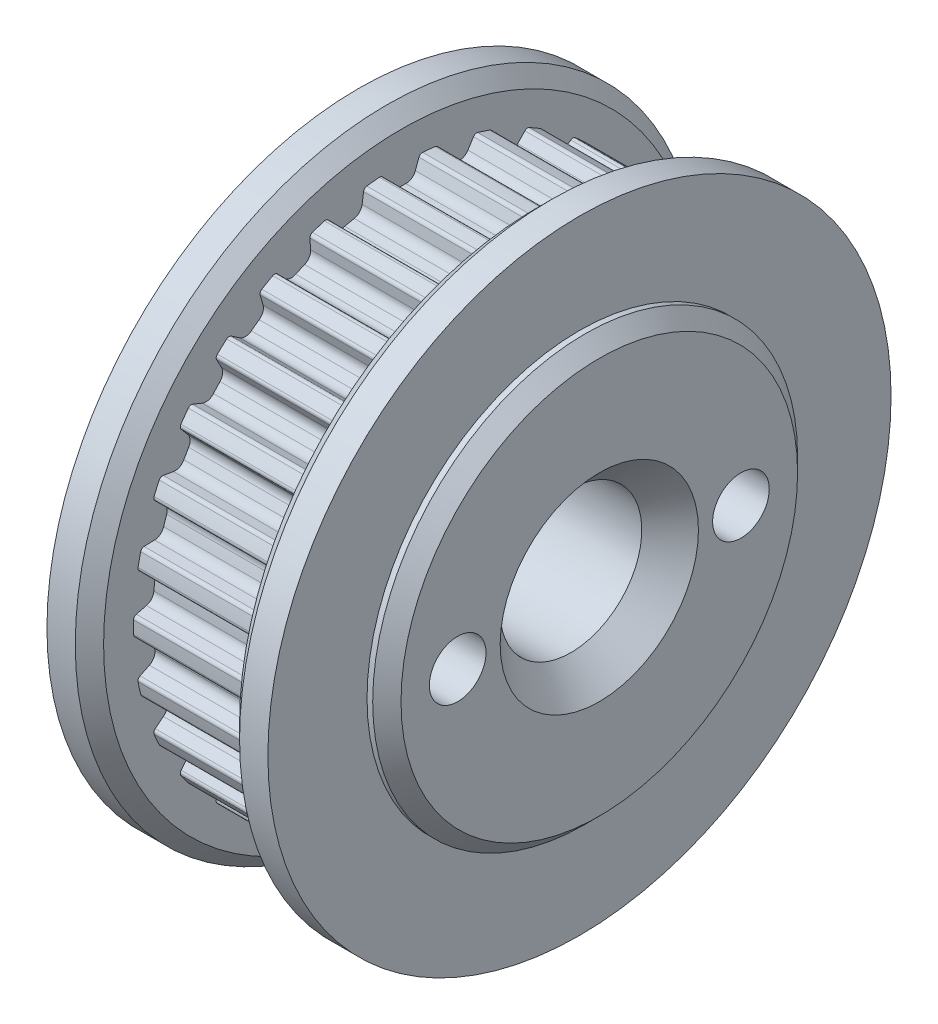
SolidWorks part; units mm, degrees
ref_plane "前视基准面" through (0, 0, 0) normal (0, 0, 1) x (1, 0, 0)
ref_plane "上视基准面" through (0, 0, 0) normal (0, 1, 0) x (1, 0, 0)
ref_plane "右视基准面" through (0, 0, 0) normal (1, 0, 0) x (0, 0, -1)
sketch "草图1" plane through (0, 0, 0) normal (0, 0, 1) x (1, 0, 0)
  line L0 (0, 0) -> (64.8368, 0) construction
  line L1 (0, 1.75) -> (0, 9.446)
  line L2 (0, 9.446) -> (4.8, 9.446)
  line L3 (4.8, 9.446) -> (4.8, 5)
  line L4 (4.8, 5) -> (7, 5)
  line L5 (7, 5) -> (7, 1.75)
  line L6 (7, 1.75) -> (0, 1.75)
  dimension "L" = 7
  dimension "B" = 4.8
  dimension "d" = 3.5
  dimension "d1" = 10
  dimension "da" = 18.892
revolve "旋转1" add sketch "草图1" angle 360 about L0
sketch "草图7" plane through (0, 0, 0) normal (-1, 0, 0) x (0, 0, 1)
  circle A1 centre (0, 0) radius 1.75 construction
  circle A2 centre (0, 0) radius 11
  circle A3 centre (0, 0) radius 1.75
  dimension "D1" = 22
extrude "凸台-拉伸1" add sketch "草图7" along normal blind 1.5
sketch "草图8" plane through (7, 0, 0) normal (1, 0, 0) x (0, 0, -1)
  circle A0 centre (0, 0) radius 2.5
  dimension "D1" = 5
extrude "切除-拉伸3" cut sketch "草图8" against normal through all
chamfer "倒角1" distance 1 angle 45 2 edges at (7, 0, -2.5) (-1.5, 0, -2.5)
ref_axis "基准轴1" through (-0.35, 0, 0) along (1, 0, 0)
sketch "草图6" plane through (0, 0, 0) normal (1, 0, 0) x (0, 0, -1)
  line L0 (0, 0) -> (0, 16.0158) construction
  line L1 (0.6325, 9.3298) -> (0.5069, 8.9846)
  line L2 (0.8947, 9.4035) -> (1.3928, 10.772)
  line L3 (-0.8947, 9.4035) -> (-1.3928, 10.772)
  line L4 (-0.6325, 9.3298) -> (-0.5069, 8.9846)
  circle A0 centre (0, 0) radius 9.446 construction
  arc A1 (0.1711, 8.7543) -> (-0.1711, 8.7543) centre (0, 0) ccw
  arc A2 (0.7652, 9.415) -> (0.8947, 9.4035) centre (0, 0) cw
  arc A3 (0.5069, 8.9846) -> (0.1711, 8.7543) centre (0.178, 9.1043) cw
  arc A4 (0.6325, 9.3298) -> (0.7652, 9.415) centre (0.7547, 9.2854) cw
  arc A5 (1.3928, 10.772) -> (-1.3928, 10.772) centre (0, 0) ccw
  arc A6 (-0.7652, 9.415) -> (-0.8947, 9.4035) centre (0, 0) ccw
  arc A7 (-0.6325, 9.3298) -> (-0.7652, 9.415) centre (-0.7547, 9.2854) ccw
  arc A8 (-0.5069, 8.9846) -> (-0.1711, 8.7543) centre (-0.178, 9.1043) ccw
  point P8 (0, 15.3258)
  point P14 (0.6662, 9.4225)
  point P16 (0.42, 8.7459)
  dimension "D1" = 8.756
  dimension "ra" = 0.13
  dimension "rf" = 0.35
  dimension "D3" = 1.4563
  dimension "D4" = 0.13
  dimension "bw" = 0.84
  dimension "angle" = 40
  dimension "hg" = 0.69
extrude "切除-拉伸2" cut sketch "草图6" along normal up to next
pattern_circular "阵列(圆周)3" count 30 over 360 about axis through (-0.35, 0, 0) along (1, 0, 0) of "切除-拉伸2"
sketch "草图10" plane through (4.8, 0, 0) normal (1, 0, 0) x (0, 0, -1)
  circle A0 centre (0, 0) radius 7.5
  circle A1 centre (0, 0) radius 5 construction
  circle A2 centre (0, 0) radius 5
  dimension "D1" = 15
extrude "凸台-拉伸3" add sketch "草图10" along normal up to surface (2.2 mm away) up to face at (7, 0, 3.5)
chamfer "倒角2" distance 0.5 angle 45 2 edges at (0, 0, 11) (7, 0, 7.5)
hole_wizard "大小mm Clearance 暗销孔1" positions "草图13" profile "草图12" hole size "Ø2.0" standard "GB" end condition through all
sketch "草图13" plane through (7, 0, 0) normal (1, 0, 0) x (0, 0, -1)
  line L0 (0, 0) -> (0, 5.1274) construction
  point P0 (-5, 0)
  point P2 (5, 0)
  dimension "D1" = 5
sketch "草图12" plane through (7, 0, 5) normal (0, 1, 0) x (0, 0, -1)
  line L0 (0, 0) -> (0, 8.5)
  line L1 (0, 8.5) -> (1, 8.5)
  line L2 (1, 8.5) -> (1, 0)
  line L5 (1, 0) -> (0, 0)
  line L11 (0, -6.35) -> (0, 107.95) construction
  dimension "通孔孔直径" = 2
  dimension "通孔孔深度" = 8.5
sketch "草图9" plane through (4.8, 0, 0) normal (1, 0, 0) x (0, 0, -1)
  circle A1 centre (0, 0) radius 11 construction
  circle A3 centre (0, 0) radius 11
  circle A4 centre (0, 0) radius 7.5 construction
  circle A5 centre (0, 0) radius 7.5
extrude "凸台-拉伸2" add sketch "草图9" along normal blind 1.5 separate body
chamfer "倒角3" distance 0.5 angle 45 2 edges at (4.8, 0, -11) (4.8, 0, -7.5)
equation "\"D4@草图6\" = \"ra@草图6\""
equation "\"D1@草图6\" = \"da@草图1\" / 2 - \"hg@草图6\" "
